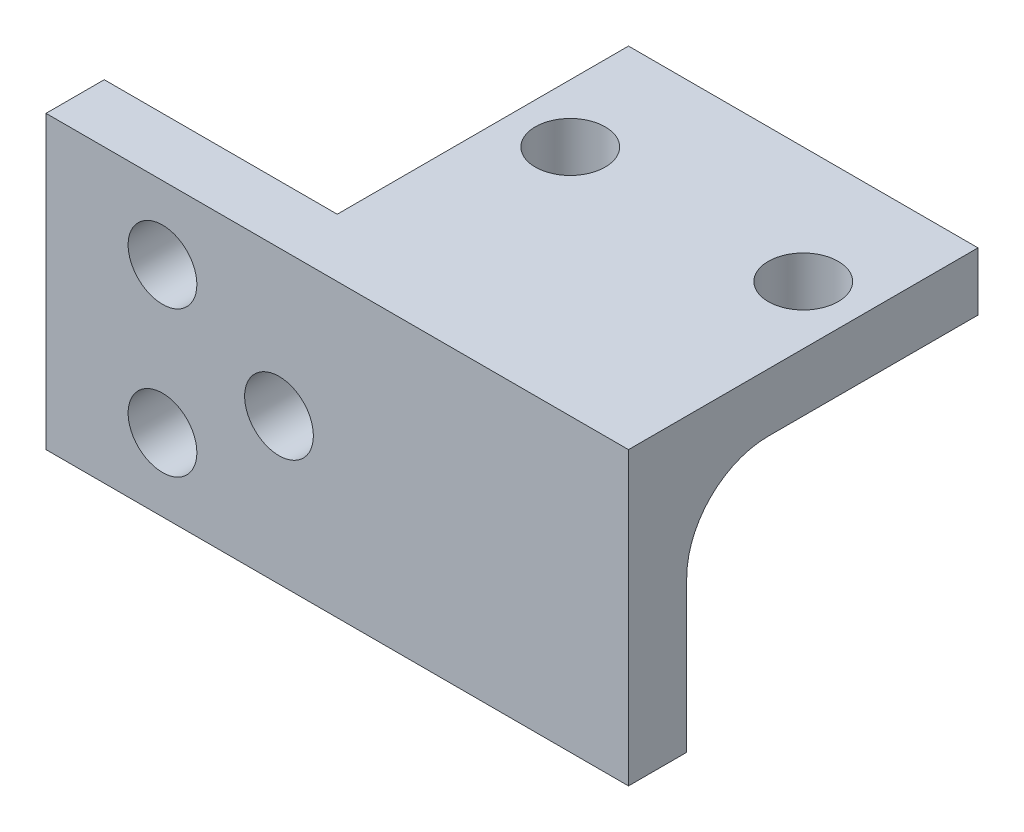
SolidWorks part; units mm, degrees
ref_plane "Alzado" through (0, 0, 0) normal (0, 0, 1) x (1, 0, 0)
ref_plane "Planta" through (0, 0, 0) normal (0, 1, 0) x (1, 0, 0)
ref_plane "Vista lateral" through (0, 0, 0) normal (1, 0, 0) x (0, 0, -1)
sketch "Croquis1" plane through (0, 0, 0) normal (0, 0, 1) x (1, 0, 0)
  line L0 (5, 25) -> (5, 0) construction
  line L1 (0, 0) -> (50, 0)
  line L2 (0, 0) -> (0, 25)
  line L3 (0, 25) -> (50, 25)
  line L4 (50, 0) -> (50, 25)
  line L5 (10, 18.75) -> (10, 6.25) construction
  circle A0 centre (10, 18.75) radius 2.95
  circle A1 centre (10, 6.25) radius 2.95
  circle A2 centre (20, 12.5) radius 2.95
  point P13 (10, 12.5)
  point P14 (0, 12.5)
  dimension "D5" = 10
  dimension "D6" = 10
  dimension "D7" = 5.9
  dimension "D1" = 50
  dimension "D2" = 25
  dimension "D3" = 5
  dimension "D4" = 12.5
extrude "Saliente-Extruir1" add sketch "Croquis1" along normal blind 5
sketch "Croquis2" plane through (0, 25, 0) normal (0, -1, 0) x (1, 0, 0)
  line L0 (50, 5) -> (50, 0) construction
  line L1 (20, 0) -> (50, 0)
  line L2 (20, 0) -> (20, -25)
  line L3 (20, -25) -> (50, -25)
  line L4 (50, 0) -> (50, -25)
  line L5 (0, 0) -> (50, 0) construction
  circle A0 centre (45, -15) radius 3
  circle A1 centre (25, -15) radius 3
  point P11 (0, 0)
  point P13 (5.1149, 0)
  dimension "D1" = 10
  dimension "D3" = 5
  dimension "D4" = 6
  dimension "D6" = 5
  dimension "D2" = 20
  dimension "D5" = 25
extrude "Saliente-Extruir2" add sketch "Croquis2" along normal blind 5
fillet "Redondeo1" radius 7 1 edges at (35, 20, 0)
